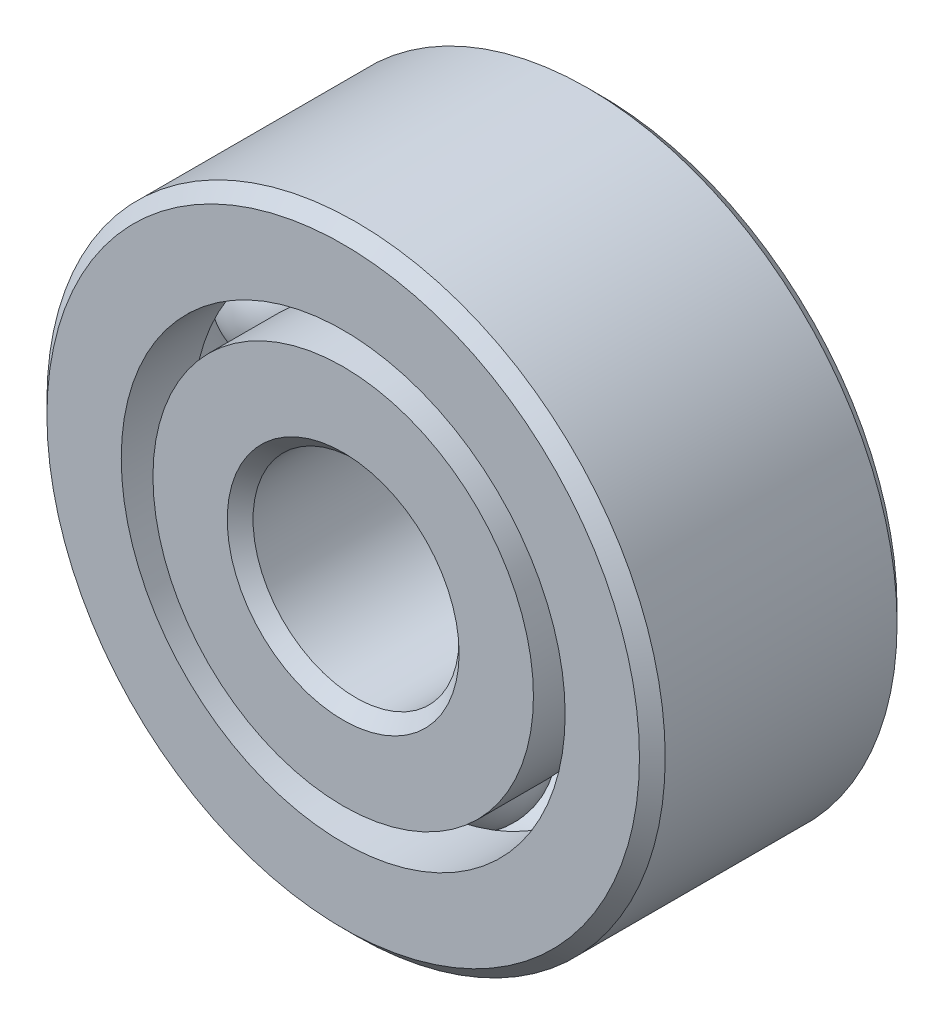
SolidWorks part; units mm, degrees
ref_plane "Front Plane" through (0, 0, 0) normal (0, 0, 1) x (1, 0, 0)
ref_plane "Top Plane" through (0, 0, 0) normal (0, 1, 0) x (1, 0, 0)
ref_plane "Right Plane" through (0, 0, 0) normal (1, 0, 0) x (0, 0, -1)
sketch "Sketch1" plane through (0, 0, 0) normal (1, 0, 0) x (0, 0, -1)
  line L0 (-1.9844, 0) -> (1.9844, 0) construction
  line L1 (0, 4.7625) -> (0, -4.7625) construction
  line L2 (1.7859, 4.7625) -> (-1.7859, 4.7625)
  line L3 (-1.7859, 4.7625) -> (-1.9844, 4.5641)
  line L4 (-1.9844, 4.5641) -> (-1.9844, 3.4192)
  line L5 (-1.9844, 3.4192) -> (-0.8819, 3.4192)
  line L6 (1.9844, 3.4192) -> (0.8819, 3.4192)
  line L7 (1.9844, 4.5641) -> (1.9844, 3.4192)
  line L8 (1.7859, 4.7625) -> (1.9844, 4.5641)
  line L9 (0, 4.7625) -> (0, 3.175) construction
  line L10 (0, 3.175) -> (0, 1.5875) construction
  arc A0 (-0.8819, 3.4192) -> (0.8819, 3.4192) centre (0, 3.175) cw
  point P14 (0, 1.5875)
  dimension "Width" = 3.9688
  dimension "OD" = 9.525
  dimension "D1" = 45
  dimension "D2" = 0.1984
  dimension "Shaft Dia" = 3.175
  dimension "D3" = 1.7639
  dimension "D4" = 0.2442
revolve "Revolve1" add sketch "Sketch1" angle 360 about L0
sketch "Sketch3" plane through (0, 0, 0) normal (1, 0, 0) x (0, 0, -1)
  line L0 (-1.9844, 2.9308) -> (-0.8819, 2.9308)
  line L1 (0, 4.7625) -> (0, -4.7625) construction
  line L2 (-1.9844, 4.5641) -> (-1.9844, 3.4192) construction
  line L3 (-1.9844, 2.9308) -> (-1.9844, 1.7859)
  line L4 (-1.7859, 4.7625) -> (-1.9844, 4.5641) construction
  line L5 (-1.9844, 1.7859) -> (-1.7859, 1.5875)
  line L6 (-1.7859, 1.5875) -> (1.7859, 1.5875)
  line L7 (1.7859, 4.7625) -> (1.7859, -4.7625) construction
  line L8 (1.7859, 1.5875) -> (1.9844, 1.7859)
  line L9 (1.9844, -4.5641) -> (1.9844, 4.5641) construction
  line L10 (1.9844, 1.7859) -> (1.9844, 2.9308)
  line L11 (1.9844, 2.9308) -> (0.8819, 2.9308)
  line L13 (1.7859, 4.7625) -> (1.9844, 4.5641) construction
  arc A0 (0.8819, 3.4192) -> (-0.8819, 3.4192) centre (0, 3.175) ccw construction
  arc A1 (0.8819, 2.9308) -> (-0.8819, 2.9308) centre (0, 3.175) cw
revolve "Revolve3" add sketch "Sketch3" angle 360 about L0
sketch "Sketch4" plane through (0, 0, 0) normal (1, 0, 0) x (0, 0, -1)
  line L0 (-0.9151, 3.175) -> (0.9151, 3.175)
  arc A2 (-0.9151, 3.175) -> (0.9151, 3.175) centre (0, 3.175) cw
  arc A3 (0.8819, 3.4192) -> (-0.8819, 3.4192) centre (0, 3.175) ccw construction
revolve "Revolve4" add sketch "Sketch4" angle 360 about L0
ref_axis "Axis1" through (0, 0, -1.9844) along (0, 0, 1)
pattern_circular "CirPattern1" count 6 every 60 about axis through (0, 0, -1.9844) along (0, 0, 1) of bodies 104
sketch "Sketch5" plane through (0, 0, 0) normal (1, 0, 0) x (0, 0, -1)
  line L0 (-1.9844, 3.4192) -> (-0.8819, 3.4192) construction
  line L1 (-1.8852, 3.4192) -> (-0.9151, 3.4192)
  line L2 (-1.8852, 3.4192) -> (-1.8852, 2.9308)
  line L3 (-1.8852, 2.9308) -> (-0.9151, 2.9308)
  line L4 (-0.9151, 3.4192) -> (-0.9151, 2.9308)
  line L5 (-1.9844, 2.9308) -> (-0.8819, 2.9308) construction
  line L6 (1.9844, 3.4192) -> (0.8819, 3.4192) construction
  line L7 (1.8852, 3.4192) -> (0.9151, 3.4192)
  line L8 (1.8852, 3.4192) -> (1.8852, 2.9308)
  line L9 (1.8852, 2.9308) -> (0.9151, 2.9308)
  line L10 (0.9151, 3.4192) -> (0.9151, 2.9308)
  line L11 (1.9844, 2.9308) -> (0.8819, 2.9308) construction
  line L12 (-1.7859, 4.7625) -> (-1.9844, 4.5641) construction
  point P18 (-1.8852, 4.6633)
revolve "Revolve5" [suppressed] add sketch "Sketch5" angle 360 about L0
equation "\"D2@Sketch1\" = \"Width@Sketch1\"*.05"
equation "\"D3@Sketch1\" = \"Width@Sketch1\"/2.25"
equation "\"D4@Sketch1\" = (((\"OD@Sketch1\"-\"Width@Sketch1\")/2)/3.25)/3.5"
equation "\"D2@CirPattern1\" = 360/\"Balls@CirPattern1\""
